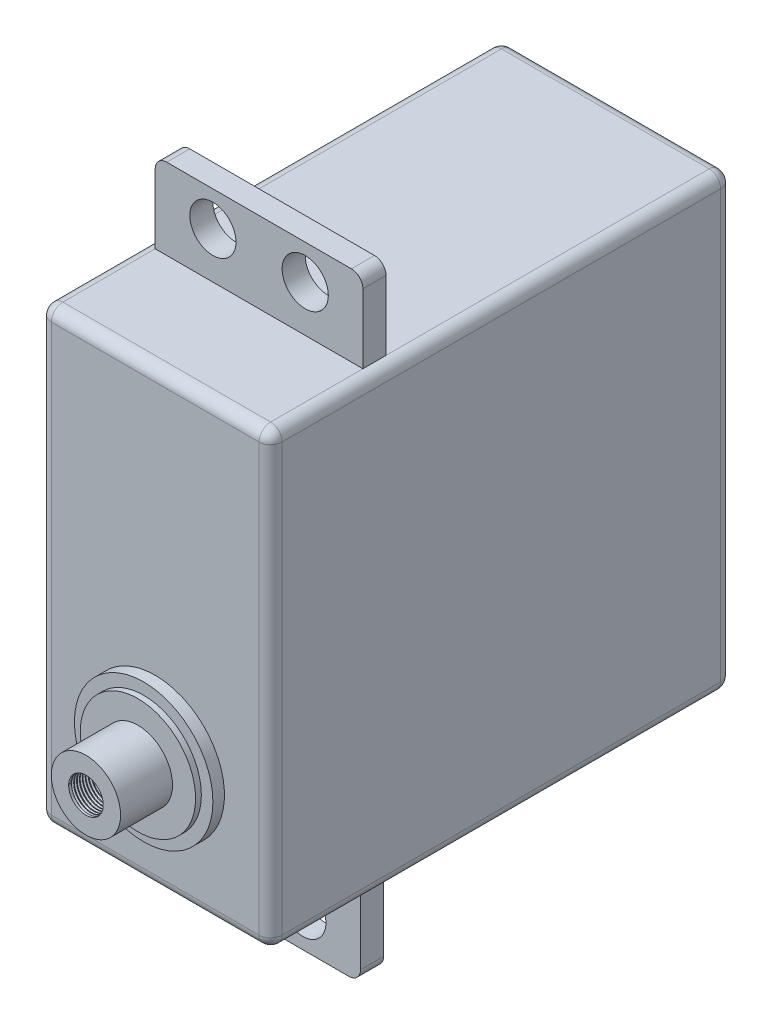
SolidWorks part; units mm, degrees
ref_plane "前视基准面" through (0, 0, 0) normal (0, 0, 1) x (1, 0, 0)
ref_plane "上视基准面" through (0, 0, 0) normal (0, 1, 0) x (1, 0, 0)
ref_plane "右视基准面" through (0, 0, 0) normal (1, 0, 0) x (0, 0, -1)
other "Configuration Table"
sketch "草图1" plane through (0, 0, 0) normal (1, 0, 0) x (0, 0, -1)
  line L1 (-20, -19.5) -> (20, -19.5)
  line L2 (-20, -19.5) -> (-20, 19.5)
  line L3 (-20, 19.5) -> (20, 19.5)
  line L4 (20, -19.5) -> (20, 19.5)
  line L5 (-20, -19.5) -> (20, 19.5) construction
  line L6 (-20, 19.5) -> (20, -19.5) construction
  point P0 (0, 0)
  dimension "D1" = 40
  dimension "D2" = 39
extrude "凸台-拉伸5" add sketch "草图1" along normal blind 20
fillet "圆角2" radius 1 12 edges at (0, 19.5, 0) (0, 0, 20) (0, -19.5, 0) (0, 0, -20) (10, -19.5, -20) (10, -19.5, 20) (20, -19.5, 0) (10, 19.5, -20) (20, 0, -20) (20, 0, 20) (10, 19.5, 20) (20, 19.5, 0)
sketch "草图5" plane through (0, -19.5, 0) normal (0, -1, 0) x (1, 0, 0)
  line L1 (19, -19) -> (19, 19) construction
  line L2 (1, 19) -> (1, -19) construction
  line L3 (19, 11.2071) -> (1, 11.2071)
  line L4 (19, 11.2071) -> (19, 9.2071)
  line L5 (19, 9.2071) -> (1, 9.2071)
  line L6 (1, 11.2071) -> (1, 9.2071)
  dimension "D1" = 2
extrude "凸台-拉伸7" add sketch "草图5" along normal blind 7 contours L4 L3 L6 L5
sketch "草图11" plane through (0, 19.5, 0) normal (0, 1, 0) x (1, 0, 0)
  line L1 (19, -19) -> (19, 19) construction
  line L2 (1, 19) -> (1, -19) construction
  line L3 (19, -11) -> (1, -11)
  line L4 (19, -11) -> (19, -9)
  line L5 (19, -9) -> (1, -9)
  line L6 (1, -11) -> (1, -9)
  dimension "D2" = 2
extrude "凸台-拉伸8" add sketch "草图11" along normal blind 7
sketch "草图13" plane through (0, 0, 11.2071) normal (0, 0, 1) x (1, 0, 0)
  circle A0 centre (6, -23.5) radius 2
  circle A1 centre (14, -23.5) radius 2
extrude "切除-拉伸1" cut sketch "草图13" against normal blind 6
sketch "草图14" plane through (0, 0, 11) normal (0, 0, 1) x (1, 0, 0)
  circle A0 centre (6, 23.5) radius 2
  circle A1 centre (14, 23.5) radius 2
  point P0 (0, 0)
extrude "切除-拉伸2" cut sketch "草图14" against normal blind 2
sketch "草图19" plane through (0, 0, 20) normal (0, 0, 1) x (1, 0, 0)
  circle A0 centre (10, -9.5) radius 3
  circle A1 centre (10, -9.5) radius 1.5
  circle A2 centre (10, -9.5) radius 6
  circle A3 centre (10, -9.5) radius 5
fillet "圆角3" radius 1 1 edges at (19, 26.5, 10)
fillet "圆角4" radius 1 1 edges at (1, 26.5, 10)
fillet "圆角5" radius 1 2 edges at (19, -26.5, 10.2071) (1, -26.5, 10.2071)
extrude "凸台-拉伸9" add sketch "草图19" along normal blind 1.5 contours A3 A0 | A0 A1 | A1 region at (7.0849, -9.5, 20) region at (10, -9.5, 20) region at (5.1414, -9.5, 20)
extrude "凸台-拉伸10" add sketch "草图19<3>" along normal blind 1 contours A2 A3 region at (4.1697, -9.5, 20)
sketch "草图19<3>" plane through (0, 0, 20) normal (0, 0, 1) x (1, 0, 0) same geometry as "草图19"
extrude "凸台-拉伸11" add sketch "草图19<4>" along normal blind 6 contours A0 | A1
sketch "草图19<4>" plane through (0, 0, 20) normal (0, 0, 1) x (1, 0, 0) same geometry as "草图19"
extrude "切除-拉伸3" cut sketch "草图19<5>" along normal blind 6 contours A1
sketch "草图19<5>" plane through (0, 0, 20) normal (0, 0, 1) x (1, 0, 0) same geometry as "草图19"
thread "螺纹线1" pitch 0.25 method cut profile "螺纹线轮廓2" start angle 0, offset 0, length 6, pitch 0.25, diameter 3
ref_plane "基准面2" through (8.5, -9.5, 26) normal (0, -1, 0) x (-1, 0, 0)
sketch "螺纹线轮廓2" plane through (8.5, -9.5, 26) normal (0, -1, 0) x (-1, 0, 0)
  line L0 (0, 0) -> (0, 0.25) construction
  line L1 (0, 0) -> (0.1353, 0.0781)
  line L2 (0.1353, 0.0781) -> (0.1353, 0.1094)
  line L3 (0.1353, 0.1094) -> (0, 0.1875)
  line L4 (0.1353, 0.0937) -> (0, 0.0937) construction
  line L11 (0, 0) -> (0, 0.1875)
  point P2 (0, 0)
  dimension "Pitch" = 0.25
  dimension "Profile_Angle" = 60
  dimension "Profile_Land" = 0.0312
  dimension "Profile_Height" = 0.1353
